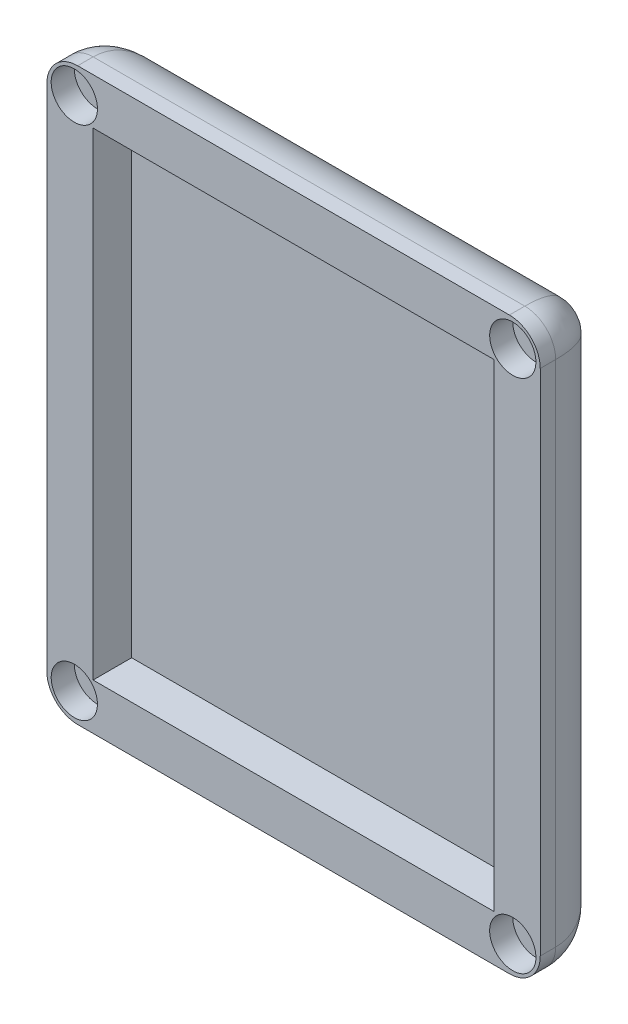
SolidWorks part; units mm, degrees
ref_plane "정면" through (0, 0, 0) normal (0, 0, 1) x (1, 0, 0)
ref_plane "윗면" through (0, 0, 0) normal (0, 1, 0) x (1, 0, 0)
ref_plane "우측면" through (0, 0, 0) normal (1, 0, 0) x (0, 0, -1)
sketch "스케치2" plane through (0, 0, 0) normal (0, 0, 1) x (1, 0, 0)
  line L1 (0, 0) -> (64, 0)
  line L2 (0, 0) -> (0, 74)
  line L3 (0, 74) -> (64, 74)
  line L4 (64, 0) -> (64, 74)
  dimension "D1" = 64
  dimension "D2" = 74
extrude "보스-돌출1" add sketch "스케치2" along normal blind 10
sketch "스케치3" plane through (0, 0, 10) normal (0, 0, 1) x (1, 0, 0)
  line L0 (32, 74) -> (32, 0) construction
  line L1 (64, 74) -> (0, 74) construction
  line L2 (0, 0) -> (64, 0) construction
  line L3 (0, 37) -> (64, 37) construction
  line L4 (0, 74) -> (0, 0) construction
  line L5 (64, 0) -> (64, 74) construction
  line L7 (6, 6) -> (58, 6)
  line L8 (6, 6) -> (6, 68)
  line L9 (6, 68) -> (58, 68)
  line L10 (58, 6) -> (58, 68)
  line L11 (32, 68) -> (32, 6) construction
  line L12 (6, 37) -> (58, 37) construction
  point P12 (32, 37)
  dimension "D1" = 52
  dimension "D2" = 62
extrude "컷-돌출1" cut sketch "스케치3" against normal blind 5
sketch "스케치4" plane through (0, 0, 5) normal (0, 0, 1) x (1, 0, 0)
  line L0 (32, 74) -> (32, 0) construction
  line L1 (64, 74) -> (0, 74) construction
  line L2 (0, 0) -> (64, 0) construction
  line L3 (0, 37) -> (64, 37) construction
  line L4 (0, 74) -> (0, 0) construction
  line L5 (64, 0) -> (64, 74) construction
  line L6 (0, 74) -> (6, 68) construction
  circle A0 centre (3.5634, 70.4366) radius 3
  circle A1 centre (60.4366, 70.4366) radius 3
  circle A2 centre (60.4366, 3.5634) radius 3
  circle A3 centre (3.5634, 3.5634) radius 3
  dimension "D1" = 6
extrude "컷-돌출3" cut sketch "스케치4" against normal blind 3 from offset 5 contours A3 | A2 | A1 | A0
fillet "필렛1" radius 4 4 edges at (0, 0, 5) (64, 0, 5) (64, 74, 5) (0, 74, 5)
fillet "필렛2" radius 8 8 edges at (1.1716, 1.1716, 0) (32, 0, 0) (62.8284, 1.1716, 0) (62.8284, 72.8284, 0) (64, 37, 0) (32, 74, 0) (0, 37, 0) (1.1716, 72.8284, 0)
